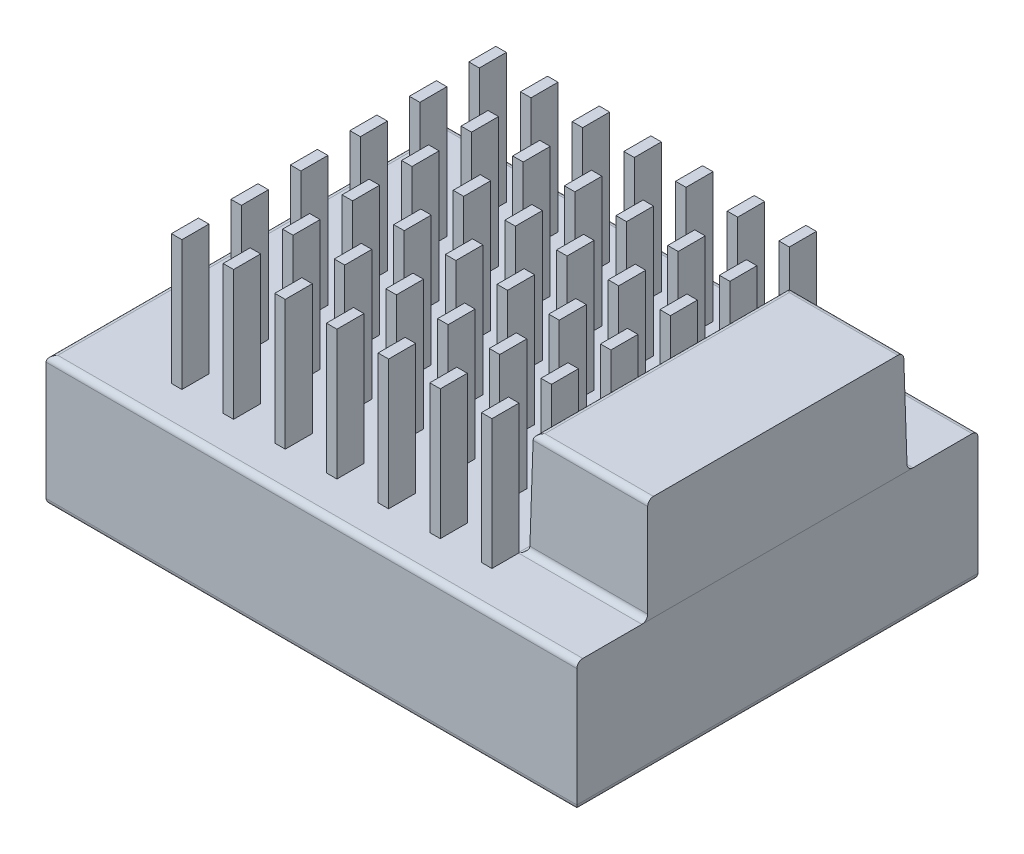
SolidWorks part; units mm, degrees
ref_plane "Front Plane" through (0, 0, 0) normal (0, 0, 1) x (1, 0, 0)
ref_plane "Top Plane" through (0, 0, 0) normal (0, 1, 0) x (1, 0, 0)
ref_plane "Right Plane" through (0, 0, 0) normal (1, 0, 0) x (0, 0, -1)
sketch "Sketch1" plane through (0, 0, 0) normal (0, 1, 0) x (1, 0, 0)
  line L1 (-22.5, -17) -> (22.5, -17)
  line L2 (-22.5, -17) -> (-22.5, 17)
  line L3 (-22.5, 17) -> (22.5, 17)
  line L4 (22.5, -17) -> (22.5, 17)
  line L5 (-22.5, -17) -> (22.5, 17) construction
  line L6 (-22.5, 17) -> (22.5, -17) construction
  point P0 (0, 0)
  dimension "D1" = 34
  dimension "D2" = 45
extrude "Boss-Extrude1" add sketch "Sketch1" along normal blind 11
sketch "Sketch2" plane through (0, 11, 0) normal (0, 1, 0) x (1, 0, 0)
  line L0 (22.5, -17) -> (22.5, 17) construction
  line L1 (22.5, 11) -> (12.5, 11)
  line L2 (22.5, 11) -> (22.5, -11)
  line L3 (22.5, -11) -> (12.5, -11)
  line L4 (12.5, 11) -> (12.5, -11)
  line L5 (12.5, 0) -> (7.1901, 0) construction
  dimension "D1" = 22
  dimension "D2" = 10
extrude "Boss-Extrude2" add sketch "Sketch2" along normal blind 8.75 draft 1
sketch "Sketch3" plane through (0, 11, 0) normal (0, 1, 0) x (1, 0, 0)
  line L0 (22.5, 17) -> (-22.5, 17) construction
  line L1 (12.0498, 3.6667) -> (11.1621, 3.6667)
  line L2 (12.0498, 3.6667) -> (12.0498, 1.375)
  line L3 (12.0498, 1.375) -> (11.1621, 1.375)
  line L4 (11.1621, 3.6667) -> (11.1621, 1.375)
  line L5 (12.0498, 8.7083) -> (11.1621, 8.7083)
  line L6 (12.0498, 8.7083) -> (12.0498, 6.4167)
  line L7 (12.0498, 6.4167) -> (11.1621, 6.4167)
  line L8 (11.1621, 8.7083) -> (11.1621, 6.4167)
  line L9 (12.0498, 13.75) -> (11.1621, 13.75)
  line L10 (12.0498, 13.75) -> (12.0498, 11.4583)
  line L11 (12.0498, 11.4583) -> (11.1621, 11.4583)
  line L12 (11.1621, 13.75) -> (11.1621, 11.4583)
  line L13 (11.1621, 7.5625) -> (7.9504, 7.5625) construction
  line L14 (7.9504, 13.75) -> (7.9504, 1.375) construction
  line L15 (18.2794, 11.4583) -> (18.2794, 8.7083) construction
  line L16 (18.9968, 6.4167) -> (18.9968, 13.75) construction
  line L17 (18.2794, 10.0833) -> (18.9968, 10.0833) construction
  point P23 (0, 0)
  point P24 (0, 0)
  dimension "D1" = 3.25
  dimension "D2" = 2.75
  dimension "D3" = 2.75
  dimension "D4" = 1.375
extrude "Boss-Extrude3" add sketch "Sketch3" along normal blind 11
mirror "Mirror1" about plane through (0, 0, 0) normal (0, 0, 1) of "Boss-Extrude3"
pattern_linear "LPattern1" count 7 spacing 4.38 along (-1, 0, 0) of "Mirror1"
fillet "Fillet1" radius 0.5 13 edges at (17.5, 19.75, 10.8473) (12.6527, 19.75, 0) (17.5, 19.75, -10.8473) (17.5, 11, -11) (12.5, 11, 0) (17.5, 11, 11) (22.5, 0, 0) (0, 0, -17) (-22.5, 0, 0) (0, 0, 17) (0, 11, 17) (-22.5, 11, 0) (0, 11, -17)
